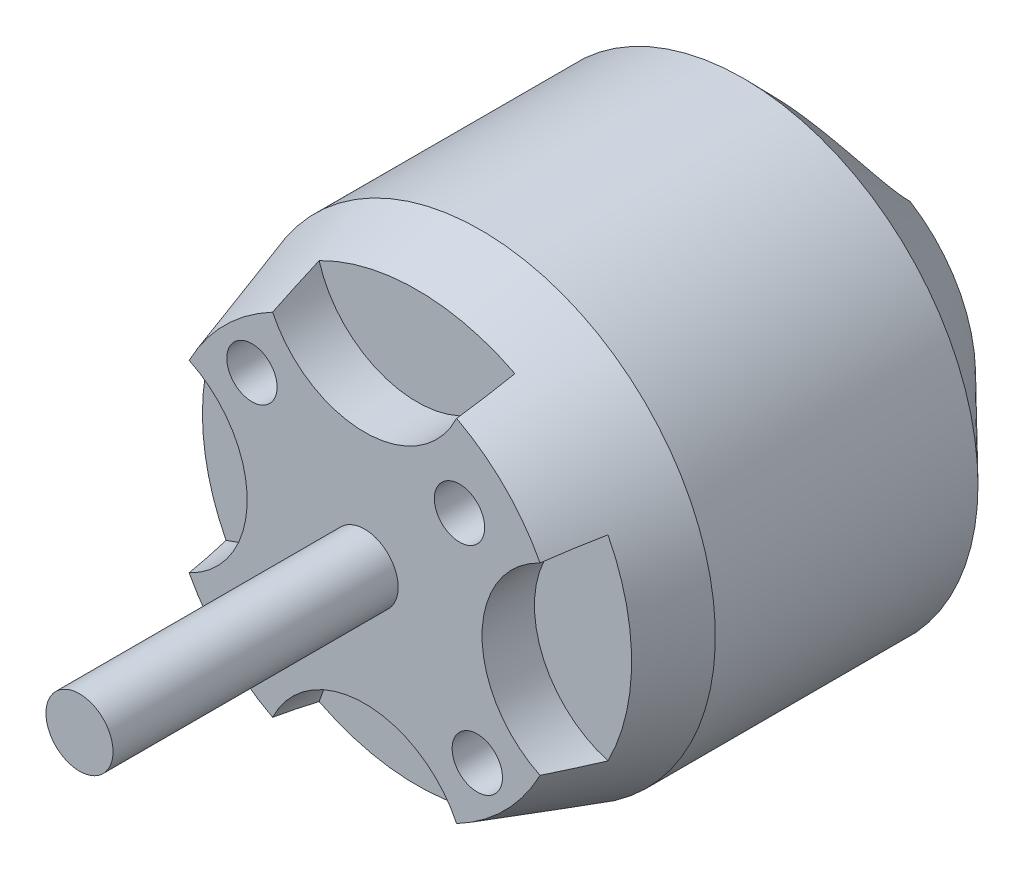
SolidWorks part; units mm, degrees
note: '?' marks a value the reader was unsure of.
ref_plane "Front Plane" through (0, 0, 0) normal (0, 0, 1) x (1, 0, 0)
ref_plane "Top Plane" through (0, 0, 0) normal (0, 1, 0) x (1, 0, 0)
ref_plane "Right Plane" through (0, 0, 0) normal (1, 0, 0) x (0, 0, -1)
sketch "Sketch1" plane through (0, 0, 0) normal (0, 0, 1) x (1, 0, 0)
  circle A0 centre (0, 0) radius 13.989
  dimension "D1" = 27.9781
extrude "Boss-Extrude1" add sketch "Sketch1" along normal blind 15.6591
ref_plane "Plane1" through (0, 0, 22.5806) normal (0, 0, 1) x (1, 0, 0)
sketch "Sketch2" plane through (0, 0, 22.5806) normal (0, 0, 1) x (1, 0, 0)
  circle A0 centre (0, 0) radius 11.811
  dimension "D1" = 23.622
loft "Loft1" add profiles "Sketch2" section edge at (13.989, 0, 15.6591) section "Sketch2" connector at (5.8606, 12.7022, 15.6591) connector at (3.7414, 11.2027, 22.5806)
ref_plane "Plane2" through (0, 0, -5.588) normal (0, 0, -1) x (-1, 0, 0)
sketch "Sketch4" plane through (0, 0, -5.588) normal (0, 0, -1) x (-1, 0, 0)
  circle A0 centre (0, 0) radius 8.255
  dimension "D1" = 16.51
loft "Loft2" add profiles "Sketch4" section edge at (13.989, 0, 0) section "Sketch4" connector at (-3.2215, 13.6131, 0) connector at (-1.5723, 8.1039, -5.588)
sketch "Sketch5" plane through (0, 0, -5.588) normal (0, 0, -1) x (-1, 0, 0)
  circle A0 centre (0, 0) radius 4.5085
  dimension "D1" = 9.017
extrude "Boss-Extrude2" add sketch "Sketch5" along normal blind 2.286
sketch "Sketch6" plane through (0, 0, -5.588) normal (0, 0, -1) x (-1, 0, 0)
  line L0 (-0.7226, 8.382) -> (0.7226, 8.382) construction
  line L1 (-0.7226, 12.2555) -> (0.7226, 12.2555)
  line L2 (-0.7226, 4.5085) -> (0.7226, 4.5085)
  line L3 (0, 0) -> (0, 8.382) construction
  arc A0 (-0.7226, 12.2555) -> (-0.7226, 4.5085) centre (-0.7226, 8.382) ccw
  arc A1 (0.7226, 4.5085) -> (0.7226, 12.2555) centre (0.7226, 8.382) ccw
  circle A2 centre (0, 0) radius 4.5085 construction
  point P2 (0, 8.382)
  dimension "D1" = 8.382
extrude "Cut-Extrude1" cut sketch "Sketch6" against normal blind 9.144
ref_axis "Axis1" through (0, 0, 15.6591) along (0, 0, -1)?
pattern_circular "CirPattern1" count 3 over 360 about axis through (0, 0, 0) along (0, 0, 1) of "Cut-Extrude1"
sketch "Sketch7" plane through (0, 0, 22.5806) normal (0, 0, 1) x (1, 0, 0)
  line L0 (0, 0) -> (0, 13.0755) construction
  circle A0 centre (0, 13.0755) radius 6.0758
extrude "Cut-Extrude2" cut sketch "Sketch7" against normal blind 3.1242
pattern_circular "CirPattern2" count 4 over 360 about axis through (0, 0, 0) along (0, 0, 1) of "Cut-Extrude2"
sketch "Sketch8" plane through (0, 0, 22.5806) normal (0, 0, 1) x (1, 0, 0)
  circle A0 centre (0, 0) radius 2
  dimension "D1" = 4
extrude "Boss-Extrude3" add sketch "Sketch8" along normal blind 17
sketch "Sketch9" plane through (0, 0, 22.5806) normal (0, 0, 1) x (1, 0, 0)
  line L0 (0, 0) -> (-8.3516, 8.3516) construction
  line L1 (0, 0) -> (8.3516, -8.3516) construction
  line L2 (0, 0) -> (8.3516, 8.3516) construction
  line L3 (0, 0) -> (-8.3516, -8.3516) construction
  arc A0 (-5.4842, 10.4605) -> (-10.4605, 5.4842) centre (0, 0) ccw construction
  arc A1 (5.4842, -10.4605) -> (10.4605, -5.4842) centre (0, 0) ccw construction
  circle A2 centre (-6.7175, 6.7175) radius 1.5
  circle A3 centre (6.7175, -6.7175) radius 1.5
  arc A4 (10.4605, 5.4842) -> (5.4842, 10.4605) centre (0, 0) ccw construction
  arc A5 (-10.4605, -5.4842) -> (-5.4842, -10.4605) centre (0, 0) ccw construction
  circle A6 centre (5.6569, 5.6569) radius 1.5
  circle A7 centre (-5.6569, -5.6569) radius 1.5
  dimension "D5" = 3
  dimension "D1" = 9.5
  dimension "D2" = 9.5
  dimension "D3" = 8
  dimension "D4" = 8
extrude "Cut-Extrude3" cut sketch "Sketch9" against normal blind 8.11
